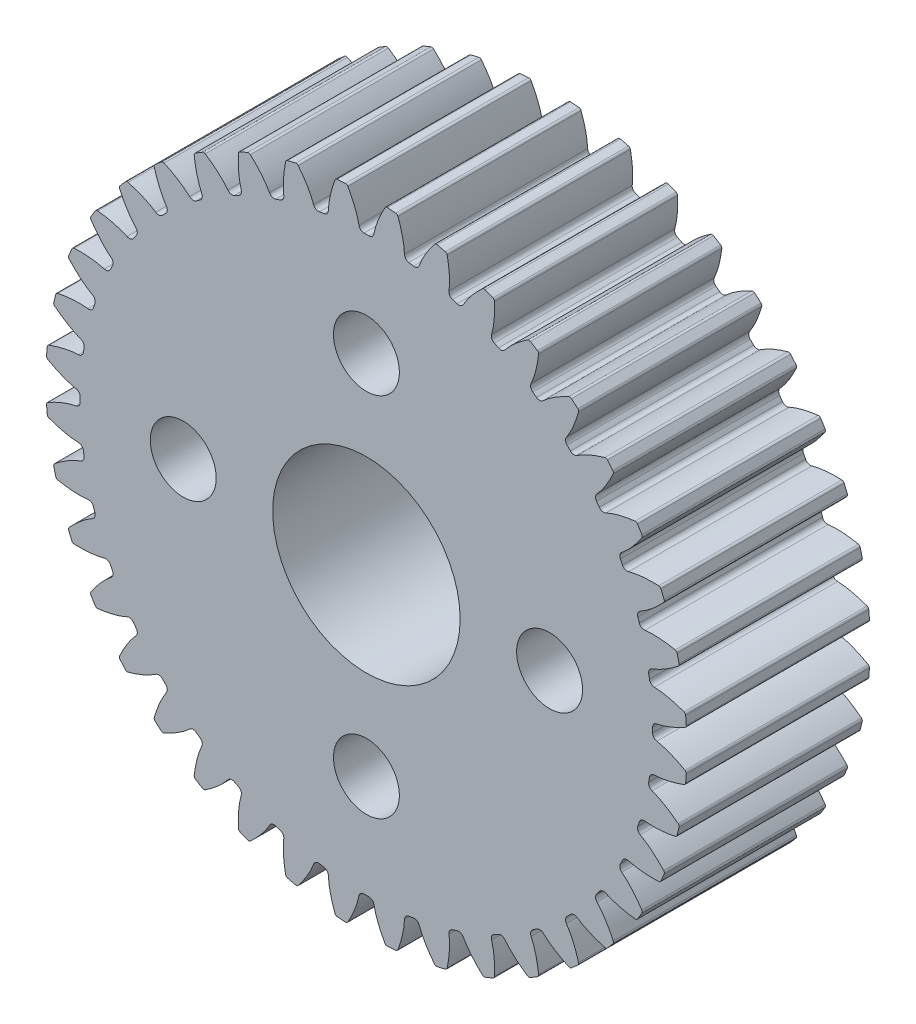
SolidWorks part; units mm, degrees
material "Alloy Steel"
ref_plane "Front" through (0, 0, 0) normal (0, 0, 1) x (1, 0, 0)
ref_plane "Top" through (0, 0, 0) normal (0, 1, 0) x (1, 0, 0)
ref_plane "Right" through (0, 0, 0) normal (1, 0, 0) x (0, 0, -1)
sketch "Sketch1" plane through (0, 0, 0) normal (0, 0, 1) x (1, 0, 0)
  circle A0 centre (0, 0) radius 22.225
  dimension "OutsideDiameter" = 44.45
extrude "Boss-Extrude1" add sketch "Sketch1" along normal blind 12.7
sketch "Sketch3" plane through (0, 0, 0) normal (0, 0, 1) x (1, 0, 0)
  line L0 (0, 0) -> (43.7181, 0) construction
  line L2 (0, 0) -> (-0.4835, 19.8379) construction
  line L3 (0, 0) -> (0.4835, 19.8379) construction
  line L4 (0.4835, 19.8379) -> (0.4846, 19.8843) construction
  line L5 (0, 0) -> (0, 61.276) construction
  line L6 (-0.4835, 19.8379) -> (-0.4846, 19.8843) construction
  circle A0 centre (0, 0) radius 22.225 construction
  circle A1 centre (0, 0) radius 21.1667 construction
  circle A2 centre (0, 0) radius 19.8902 construction
  arc A3 (0.4835, 19.8379) -> (-0.4835, 19.8379) centre (0, 0) ccw construction
  arc A5 (1.3422, 22.1844) -> (-1.3422, 22.1844) centre (0, 0) ccw
  spline S0 degree 4 poles (-0.4846, 19.8843) (-0.4847, 19.8879) (-0.4852, 19.8982) (-0.4866, 19.9175) (-0.4895, 19.9491) (-0.4942, 19.9892) (-0.5014, 20.0411) (-0.5113, 20.1021) (-0.5237, 20.1691) (-0.5389, 20.2419) (-0.5555, 20.3144) (-0.5734, 20.3867) (-0.5925, 20.4586) (-0.617, 20.5455) (-0.6484, 20.6496) (-0.6881, 20.7711) (-0.7365, 20.9085) (-0.7895, 21.0483) (-0.8447, 21.1854) (-0.904, 21.3237) (-0.9638, 21.4571) (-1.0294, 21.5954) (-1.0919, 21.7228) (-1.1658, 21.865) (-1.2266, 21.9797) (-1.311, 22.1304) (-1.3621, 22.2193) (-1.4233, 22.3231) (-1.4513, 22.3691) (-1.4685, 22.3974) knots 0 0 0 0 0 0.005377 0.015084 0.028532 0.04661 0.064855 0.092111 0.119476 0.146842 0.174209 0.201575 0.228941 0.256307 0.307035 0.361767 0.4165 0.471232 0.525964 0.580697 0.635429 0.690161 0.744894 0.799626 0.854358 0.909091 0.954545 1 1 1 1 1 construction
  spline S1 degree 4 poles (-0.4846, 19.8843) (-0.4847, 19.8879) (-0.4852, 19.8982) (-0.4866, 19.9175) (-0.4895, 19.9491) (-0.4942, 19.9892) (-0.5014, 20.0411) (-0.5113, 20.1021) (-0.5237, 20.1691) (-0.5389, 20.2419) (-0.5555, 20.3144) (-0.5734, 20.3867) (-0.5925, 20.4586) (-0.617, 20.5455) (-0.6484, 20.6496) (-0.6881, 20.7711) (-0.7365, 20.9085) (-0.7895, 21.0483) (-0.8447, 21.1854) (-0.904, 21.3237) (-0.9638, 21.4571) (-1.0294, 21.5954) (-1.0919, 21.7228) (-1.1658, 21.865) (-1.2266, 21.9797) (-1.2927, 22.0977) (-1.3253, 22.1551) (-1.3422, 22.1844) knots 0 0 0 0 0 0.005377 0.015084 0.028532 0.04661 0.064855 0.092111 0.119476 0.146842 0.174209 0.201575 0.228941 0.256307 0.307035 0.361767 0.4165 0.471232 0.525964 0.580697 0.635429 0.690161 0.744894 0.799626 0.854358 0.909091 0.909091 0.909091 0.909091 0.909091
  spline S2 degree 4 poles (0.4846, 19.8843) (0.4847, 19.8879) (0.4852, 19.8982) (0.4866, 19.9175) (0.4895, 19.9491) (0.4942, 19.9892) (0.5014, 20.0411) (0.5113, 20.1021) (0.5237, 20.1691) (0.5389, 20.2419) (0.5555, 20.3144) (0.5734, 20.3867) (0.5925, 20.4586) (0.617, 20.5455) (0.6484, 20.6496) (0.6881, 20.7711) (0.7365, 20.9085) (0.7895, 21.0483) (0.8447, 21.1854) (0.904, 21.3237) (0.9638, 21.4571) (1.0294, 21.5954) (1.0919, 21.7228) (1.1658, 21.865) (1.2266, 21.9797) (1.311, 22.1304) (1.3621, 22.2193) (1.4233, 22.3231) (1.4513, 22.3691) (1.4685, 22.3974) knots 0 0 0 0 0 0.005377 0.015084 0.028532 0.04661 0.064855 0.092111 0.119476 0.146842 0.174209 0.201575 0.228941 0.256307 0.307035 0.361767 0.4165 0.471232 0.525964 0.580697 0.635429 0.690161 0.744894 0.799626 0.854358 0.909091 0.954545 1 1 1 1 1 construction
  spline S3 degree 4 poles (0.4846, 19.8843) (0.4847, 19.8879) (0.4852, 19.8982) (0.4866, 19.9175) (0.4895, 19.9491) (0.4942, 19.9892) (0.5014, 20.0411) (0.5113, 20.1021) (0.5237, 20.1691) (0.5389, 20.2419) (0.5555, 20.3144) (0.5734, 20.3867) (0.5925, 20.4586) (0.617, 20.5455) (0.6484, 20.6496) (0.6881, 20.7711) (0.7365, 20.9085) (0.7895, 21.0483) (0.8447, 21.1854) (0.904, 21.3237) (0.9638, 21.4571) (1.0294, 21.5954) (1.0919, 21.7228) (1.1658, 21.865) (1.2266, 21.9797) (1.2927, 22.0977) (1.3253, 22.1551) (1.3422, 22.1844) knots 0 0 0 0 0 0.005377 0.015084 0.028532 0.04661 0.064855 0.092111 0.119476 0.146842 0.174209 0.201575 0.228941 0.256307 0.307035 0.361767 0.4165 0.471232 0.525964 0.580697 0.635429 0.690161 0.744894 0.799626 0.854358 0.909091 0.909091 0.909091 0.909091 0.909091
  point P0 (0, 19.8438)
  dimension "OutsideDiameter" = 44.45
  dimension "PitchCircle" = 42.3333
  dimension "BaseCircle" = 39.7803
  dimension "DedendumCircle" = 39.6875
sketch "DCLTBC" plane through (0, 0, 0) normal (0, 0, 1) x (1, 0, 0)
  line L0 (0, 0) -> (41.04, 0) construction
  line L1 (-0.4835, 19.8379) -> (-0.4846, 19.8843) construction
  line L2 (0.4835, 19.8379) -> (0.4846, 19.8843) construction
  line L3 (-0.4835, 19.8379) -> (-0.4846, 19.8843)
  line L4 (0.4835, 19.8379) -> (0.4846, 19.8843)
  line L5 (0, 0) -> (0, 104.9356) construction
  circle A0 centre (0, 0) radius 22.225
  circle A1 centre (0, 0) radius 21.1667 construction
  circle A2 centre (0, 0) radius 19.8902 construction
  arc A3 (0.4835, 19.8379) -> (-0.4835, 19.8379) centre (0, 0) ccw construction
  arc A4 (0.4835, 19.8379) -> (-0.4835, 19.8379) centre (0, 0) ccw
  spline S0 degree 4 poles (-1998.0236, -76.1893) (-19.2856, 17.912) (-0.6992, 18.847) (-0.4393, 19.4056) (-0.4895, 19.9491) (-0.4942, 19.9892) (-0.5014, 20.0411) (-0.5113, 20.1021) (-0.5237, 20.1691) (-0.5389, 20.2419) (-0.5555, 20.3144) (-0.5734, 20.3867) (-0.5925, 20.4586) (-0.617, 20.5455) (-0.6484, 20.6496) (-0.6881, 20.7711) (-0.7365, 20.9085) (-0.7895, 21.0483) (-0.8447, 21.1854) (-0.904, 21.3237) (-0.9638, 21.4571) (-1.0294, 21.5954) (-1.0919, 21.7228) (-1.1658, 21.865) (-1.5253, 22.5431) (-3.0383, 25.0196) (20.4885, -16.0572) (-1000.4715, 1754.6896) knots -0.756275 -0.756275 -0.756275 -0.756275 -0.756275 0.005377 0.015084 0.028532 0.04661 0.064855 0.092111 0.119476 0.146842 0.174209 0.201575 0.228941 0.256307 0.307035 0.361767 0.4165 0.471232 0.525964 0.580697 0.635429 0.690161 0.744894 0.799626 0.854358 1.984824 1.984824 1.984824 1.984824 1.984824 only from (-0.4846, 19.8843) to (-1.3422, 22.1844) construction
  spline S1 degree 4 poles (1998.0236, -76.1893) (19.2856, 17.912) (0.6992, 18.847) (0.4393, 19.4056) (0.4895, 19.9491) (0.4942, 19.9892) (0.5014, 20.0411) (0.5113, 20.1021) (0.5237, 20.1691) (0.5389, 20.2419) (0.5555, 20.3144) (0.5734, 20.3867) (0.5925, 20.4586) (0.617, 20.5455) (0.6484, 20.6496) (0.6881, 20.7711) (0.7365, 20.9085) (0.7895, 21.0483) (0.8447, 21.1854) (0.904, 21.3237) (0.9638, 21.4571) (1.0294, 21.5954) (1.0919, 21.7228) (1.1658, 21.865) (1.5253, 22.5431) (3.0383, 25.0196) (-20.4885, -16.0572) (1000.4715, 1754.6896) knots -0.756275 -0.756275 -0.756275 -0.756275 -0.756275 0.005377 0.015084 0.028532 0.04661 0.064855 0.092111 0.119476 0.146842 0.174209 0.201575 0.228941 0.256307 0.307035 0.361767 0.4165 0.471232 0.525964 0.580697 0.635429 0.690161 0.744894 0.799626 0.854358 1.984824 1.984824 1.984824 1.984824 1.984824 only from (0.4846, 19.8843) to (1.3422, 22.1844) construction
  spline S2 degree 4 poles (-0.4846, 19.8843) (-0.4847, 19.8879) (-0.4852, 19.8982) (-0.4866, 19.9175) (-0.4895, 19.9491) (-0.4942, 19.9892) (-0.5014, 20.0411) (-0.5113, 20.1021) (-0.5237, 20.1691) (-0.5389, 20.2419) (-0.5555, 20.3144) (-0.5734, 20.3867) (-0.5925, 20.4586) (-0.617, 20.5455) (-0.6484, 20.6496) (-0.6881, 20.7711) (-0.7365, 20.9085) (-0.7895, 21.0483) (-0.8447, 21.1854) (-0.904, 21.3237) (-0.9638, 21.4571) (-1.0294, 21.5954) (-1.0919, 21.7228) (-1.1658, 21.865) (-1.2266, 21.9797) (-1.2927, 22.0977) (-1.3253, 22.1551) (-1.3422, 22.1844) knots 0 0 0 0 0 0.005377 0.015084 0.028532 0.04661 0.064855 0.092111 0.119476 0.146842 0.174209 0.201575 0.228941 0.256307 0.307035 0.361767 0.4165 0.471232 0.525964 0.580697 0.635429 0.690161 0.744894 0.799626 0.854358 0.909091 0.909091 0.909091 0.909091 0.909091
  spline S3 degree 4 poles (0.4846, 19.8843) (0.4847, 19.8879) (0.4852, 19.8982) (0.4866, 19.9175) (0.4895, 19.9491) (0.4942, 19.9892) (0.5014, 20.0411) (0.5113, 20.1021) (0.5237, 20.1691) (0.5389, 20.2419) (0.5555, 20.3144) (0.5734, 20.3867) (0.5925, 20.4586) (0.617, 20.5455) (0.6484, 20.6496) (0.6881, 20.7711) (0.7365, 20.9085) (0.7895, 21.0483) (0.8447, 21.1854) (0.904, 21.3237) (0.9638, 21.4571) (1.0294, 21.5954) (1.0919, 21.7228) (1.1658, 21.865) (1.2266, 21.9797) (1.2927, 22.0977) (1.3253, 22.1551) (1.3422, 22.1844) knots 0 0 0 0 0 0.005377 0.015084 0.028532 0.04661 0.064855 0.092111 0.119476 0.146842 0.174209 0.201575 0.228941 0.256307 0.307035 0.361767 0.4165 0.471232 0.525964 0.580697 0.635429 0.690161 0.744894 0.799626 0.854358 0.909091 0.909091 0.909091 0.909091 0.909091
  dimension "OutsideDiameter" = 44.45
  dimension "PitchCircle" = 42.3333
  dimension "BaseCircle" = 39.7803
extrude "Cut-Extrude-DCLTBC" cut sketch "DCLTBC" along normal through all contours L4 S3 A0 S2 L3 A4 region at (0, 21.2409, 0)
fillet "Fillet-Tip-DCLTBC" radius 0.1775 2 edges at (1.3422, 22.1844, 6.35) (-1.3422, 22.1844, 6.35)
fillet "Fillet-Root-DCLTBC" radius 0.3551 2 edges at (-0.4835, 19.8379, 6.35) (0.4835, 19.8379, 6.35)
pattern_circular "CirPattern-DCLTBC" count 40 over 360 about axis through (0, 0, 12.7) along (0, 0, 1) of "Cut-Extrude-DCLTBC", "Fillet-Tip-DCLTBC", "Fillet-Root-DCLTBC"
sketch "DCGTBC" [suppressed] plane through (0, 0, 0) normal (0, 0, 1) x (1, 0, 0)
  line L0 (0, 0) -> (41.04, 0) construction
  line L1 (-46.1259, 4.0355) -> (0, 0) construction
  line L2 (0, 0) -> (46.1259, 4.0355) construction
  line L3 (0, 0) -> (-16.5124, 0)
  line L5 (0, 0) -> (0, 104.9356) construction
  circle A0 centre (0, 0) radius 48.6833
  circle A1 centre (0, 0) radius 47.625 construction
  circle A2 centre (0, 0) radius 44.7529 construction
  arc A3 (0.118, 46.3019) -> (-0.118, 46.3019) centre (0, 0) ccw construction
  arc A11 (46.1259, 4.0355) -> (-46.1259, 4.0355) centre (0, 0) ccw
  spline S4 degree 4 poles (999.5815, 12.6216) (12.5191, 42.79) (0.2993, 43.4561) (0.0763, 44.1558) (0.1191, 44.8605) (0.1245, 44.9274) (0.1332, 45.0138) (0.1455, 45.1157) (0.1612, 45.2277) (0.1807, 45.3496) (0.2021, 45.4712) (0.2255, 45.5925) (0.2505, 45.7134) (0.2829, 45.8599) (0.3247, 46.0355) (0.3777, 46.2409) (0.4428, 46.4738) (0.5145, 46.7113) (0.5894, 46.945) (0.6702, 47.1812) (0.7519, 47.4098) (0.842, 47.6473) (0.9278, 47.8666) (1.0298, 48.1124) (1.4163, 49.0258) (2.7458, 51.7852) (-10.8917, 21.8496) (419.1002, 957.173) knots -0.579054 -0.579054 -0.579054 -0.579054 -0.579054 0.005377 0.015084 0.028532 0.04661 0.064855 0.092111 0.119476 0.146842 0.174209 0.201575 0.228941 0.256307 0.307035 0.361767 0.4165 0.471232 0.525964 0.580697 0.635429 0.690161 0.744894 0.799626 0.854358 1.698137 1.698137 1.698137 1.698137 1.698137 only from (0.1141, 44.7527) to (1.274, 48.6667) construction
  spline S5 degree 4 poles (-999.5815, 12.6216) (-12.5191, 42.79) (-0.2993, 43.4561) (-0.0763, 44.1558) (-0.1191, 44.8605) (-0.1245, 44.9274) (-0.1332, 45.0138) (-0.1455, 45.1157) (-0.1612, 45.2277) (-0.1807, 45.3496) (-0.2021, 45.4712) (-0.2255, 45.5925) (-0.2505, 45.7134) (-0.2829, 45.8599) (-0.3247, 46.0355) (-0.3777, 46.2409) (-0.4428, 46.4738) (-0.5145, 46.7113) (-0.5894, 46.945) (-0.6702, 47.1812) (-0.7519, 47.4098) (-0.842, 47.6473) (-0.9278, 47.8666) (-1.0298, 48.1124) (-1.4163, 49.0258) (-2.7458, 51.7852) (10.8917, 21.8496) (-419.1002, 957.173) knots -0.579054 -0.579054 -0.579054 -0.579054 -0.579054 0.005377 0.015084 0.028532 0.04661 0.064855 0.092111 0.119476 0.146842 0.174209 0.201575 0.228941 0.256307 0.307035 0.361767 0.4165 0.471232 0.525964 0.580697 0.635429 0.690161 0.744894 0.799626 0.854358 1.698137 1.698137 1.698137 1.698137 1.698137 only from (-0.1141, 44.7527) to (-1.274, 48.6667) construction
  spline S6 degree 4 poles (0.1141, 44.7527) (0.1141, 44.7588) (0.1145, 44.7758) (0.1159, 44.808) (0.1191, 44.8605) (0.1245, 44.9274) (0.1332, 45.0138) (0.1455, 45.1157) (0.1612, 45.2277) (0.1807, 45.3496) (0.2021, 45.4712) (0.2255, 45.5925) (0.2505, 45.7134) (0.2829, 45.8599) (0.3247, 46.0355) (0.3777, 46.2409) (0.4428, 46.4738) (0.5145, 46.7113) (0.5894, 46.945) (0.6702, 47.1812) (0.7519, 47.4098) (0.842, 47.6473) (0.9278, 47.8666) (1.0298, 48.1124) (1.1137, 48.3108) (1.2053, 48.5158) (1.2506, 48.6156) (1.274, 48.6667) knots 0 0 0 0 0 0.005377 0.015084 0.028532 0.04661 0.064855 0.092111 0.119476 0.146842 0.174209 0.201575 0.228941 0.256307 0.307035 0.361767 0.4165 0.471232 0.525964 0.580697 0.635429 0.690161 0.744894 0.799626 0.854358 0.909091 0.909091 0.909091 0.909091 0.909091
  spline S7 degree 4 poles (-0.1141, 44.7527) (-0.1141, 44.7588) (-0.1145, 44.7758) (-0.1159, 44.808) (-0.1191, 44.8605) (-0.1245, 44.9274) (-0.1332, 45.0138) (-0.1455, 45.1157) (-0.1612, 45.2277) (-0.1807, 45.3496) (-0.2021, 45.4712) (-0.2255, 45.5925) (-0.2505, 45.7134) (-0.2829, 45.8599) (-0.3247, 46.0355) (-0.3777, 46.2409) (-0.4428, 46.4738) (-0.5145, 46.7113) (-0.5894, 46.945) (-0.6702, 47.1812) (-0.7519, 47.4098) (-0.842, 47.6473) (-0.9278, 47.8666) (-1.0298, 48.1124) (-1.1137, 48.3108) (-1.2053, 48.5158) (-1.2506, 48.6156) (-1.274, 48.6667) knots 0 0 0 0 0 0.005377 0.015084 0.028532 0.04661 0.064855 0.092111 0.119476 0.146842 0.174209 0.201575 0.228941 0.256307 0.307035 0.361767 0.4165 0.471232 0.525964 0.580697 0.635429 0.690161 0.744894 0.799626 0.854358 0.909091 0.909091 0.909091 0.909091 0.909091
  dimension "D1" = 5
  dimension "D2" = 5
  dimension "OutsideDiameter" = 44.45
  dimension "PitchCircle" = 42.3333
  dimension "BaseCircle" = 39.7803
extrude "Cut-Extrude-DCGTBC" [suppressed] cut sketch "DCGTBC" along normal through all
fillet "Fillet-Tip-DCGTBC" [suppressed] radius 0.1775
pattern_circular "CirPattern-DCGTBC" [suppressed] count 40 over 360 of bodies 112
sketch "Sketch4" plane through (0, 0, 12.7) normal (0, 0, 1) x (1, 0, 0)
  circle A1 centre (0, 0) radius 6.5
extrude "Cut-Extrude2" cut sketch "Sketch4" against normal through all
sketch "Sketch5" plane through (0, 0, 12.7) normal (0, 0, 1) x (1, 0, 0)
  circle A0 centre (-12.7, 0) radius 2.286
  circle A1 centre (0, 12.7) radius 2.286
  circle A2 centre (12.7, 0) radius 2.286
  circle A3 centre (0, -12.7) radius 2.286
  point P12 (0, 0)
  dimension "D2" = 4.572
  dimension "D1" = 12.7
  dimension "D3" = 4
extrude "Cut-Extrude3" cut sketch "Sketch5" against normal through all
equation "\"DiametralPitch\"= 24'Diametral Pitch"
equation "\"NumTeeth\"= 40'Number of Teeth"
equation "\"PressureAngle\"= 20deg'Pressure Angle"
equation "\"Addendum\"= 1 / \"DiametralPitch\"'Addendum"
equation "\"Dedendum\"= 1.25 / \"DiametralPitch\"'Dedendum"
equation "\"WorkingDepth\"= 2 / \"DiametralPitch\"'Working Depth - here for REF (Not used in building model)"
equation "\"WholeDepth\"= 2.25 / \"DiametralPitch\"'Whole Depth - here for REF (Not used in building model)"
equation "\"Clearance\"= .25 / \"DiametralPitch\"'Clearance"
equation "\"CircularPitch\"= pi / \"DiametralPitch\"'Circular Pitch - here for REF (Not used in building model)"
equation "\"PitchCircle\"= \"NumTeeth\" / \"DiametralPitch\"'Pitch Circle - or - Pitch Diameter"
equation "\"OutsideDiameter\"= ( \"NumTeeth\" + 2 ) / \"DiametralPitch\"'Outside Diameter"
equation "\"Fillet_Root\"= \"Clearance\" * cos ( \"PressureAngle\" ) * tan ( ( 90 + \"PressureAngle\" ) / 2 ) 'Fillet Root"
equation "\"AddendumCircle\"= \"PitchCircle\" + ( 2 * \"Addendum\" )'Addendum Circle - or - Addendum Diameter"
equation "\"DedendumCircle\"= \"PitchCircle\" - ( 2 * \"Dedendum\" )'Dedendum Circle - or - Dedendum Diameter"
equation "\"BaseCircle\"= \"PitchCircle\" * cos ( \"PressureAngle\" )'Base Circle - Base Diameter"
equation "\"PitchAngle\"= 360deg / \"NumTeeth\"'Pitch Angle"
equation "\"Alpha\"= sqr ( \"PitchCircle\" ^ 2 - \"BaseCircle\" ^ 2 ) / \"BaseCircle\" * 180 / PI - \"PressureAngle\"'Alpha - Used for Calculating Beta"
equation "\"Beta\"= ( \"PitchAngle\" / 4 - ( \"Alpha\" - 90 ) )'Beta - Used in definition of the parameters for the parametric equation driven curve"
equation "\"Gamma\"= ( \"PitchAngle\" / 4 - ( \"Alpha\" + 90 ) )'Gamma - Used in definition of the parameters for the parametric equation driven curve"
equation "\"Phi\"= sqr ( ( \"AddendumCircle\" / 2 ) ^ 2 - ( \"BaseCircle\" / 2 ) ^ 2 ) / ( \"BaseCircle\" / 2 )'Phi - Used in definition of the parameters for the parametric equation driven curve"
equation "\"DCGTBC\"= iif ( \"DedendumCircle\" > \"BaseCircle\" , \"unsuppressed\" , \"suppressed\" )'if Dedendum Circle IS GREATER THAN BaseCircle THEN UnsuppressORSuppress FEATURE"
equation "\"DCLTBC\"= iif ( \"DedendumCircle\" - .002 > \"BaseCircle\" , \"suppressed\" , \"unsuppressed\" )'if Dedendum Circle - .002 IS GREATER THAN BaseCircle THEN SuppressORUnsuppress FEATURE"
equation "\"Cut-Extrude-DCGTBC\"= iif ( \"DedendumCircle\" > \"BaseCircle\" , \"unsuppressed\" , \"suppressed\" )'if Dedendum Circle IS GREATER THAN BaseCircle THEN UnsuppressORSuppress FEATURE"
equation "\"Cut-Extrude-DCLTBC\"= iif ( \"DedendumCircle\" - .002 > \"BaseCircle\" , \"suppressed\" , \"unsuppressed\" )'if Dedendum Circle - .002 IS GREATER THAN BaseCircle THEN SuppressORUnsuppress FEATURE"
equation "\"CirPattern-DCGTBC\"= iif ( \"DedendumCircle\" > \"BaseCircle\" , \"unsuppressed\" , \"suppressed\" )'if Dedendum Circle IS GREATER THAN BaseCircle THEN UnsuppressORSuppress FEATURE"
equation "\"CirPattern-DCLTBC\"= iif ( \"DedendumCircle\" - .002 > \"BaseCircle\" , \"suppressed\" , \"unsuppressed\" )'if Dedendum Circle - .002 IS GREATER THAN BaseCircle THEN SuppressORUnsuppress FEATURE"
equation "\"Fillet-Tip-DCGTBC\"= iif ( \"DedendumCircle\" > \"BaseCircle\" , \"unsuppressed\" , \"suppressed\" )'if Dedendum Circle IS GREATER THAN BaseCircle THEN UnsuppressORSuppress FEATURE"
equation "\"Fillet-Tip-DCLTBC\"= iif ( \"DedendumCircle\" - .002 > \"BaseCircle\" , \"suppressed\" , \"unsuppressed\" )'if Dedendum Circle - .002 IS GREATER THAN BaseCircle THEN SuppressORUnsuppress FEATURE"
equation "\"Fillet-Root-DCLTBC\"= iif ( \"DedendumCircle\" - .002 > \"BaseCircle\" , \"suppressed\" , \"unsuppressed\" )'if Dedendum Circle - .002 IS GREATER THAN BaseCircle THEN SuppressORUnsuppress FEATURE"
equation "\"D1@CirPattern-DCGTBC\"= \"NumTeeth\"'Number of Teeth"
equation "\"D1@CirPattern-DCLTBC\"= \"NumTeeth\"'Number of Teeth"
equation "\"D1@Fillet-Tip-DCGTBC\"= \"Fillet_Root\" / 2 'Tip Rad For Large No of Teeth"
equation "\"D1@Fillet-Tip-DCLTBC\"=\"Fillet_Root\" / 2'Tip Rad For Small No of Teeth"
equation "\"D1@Fillet-Root-DCLTBC\"= \"Fillet_Root\"'Fillet Root"
